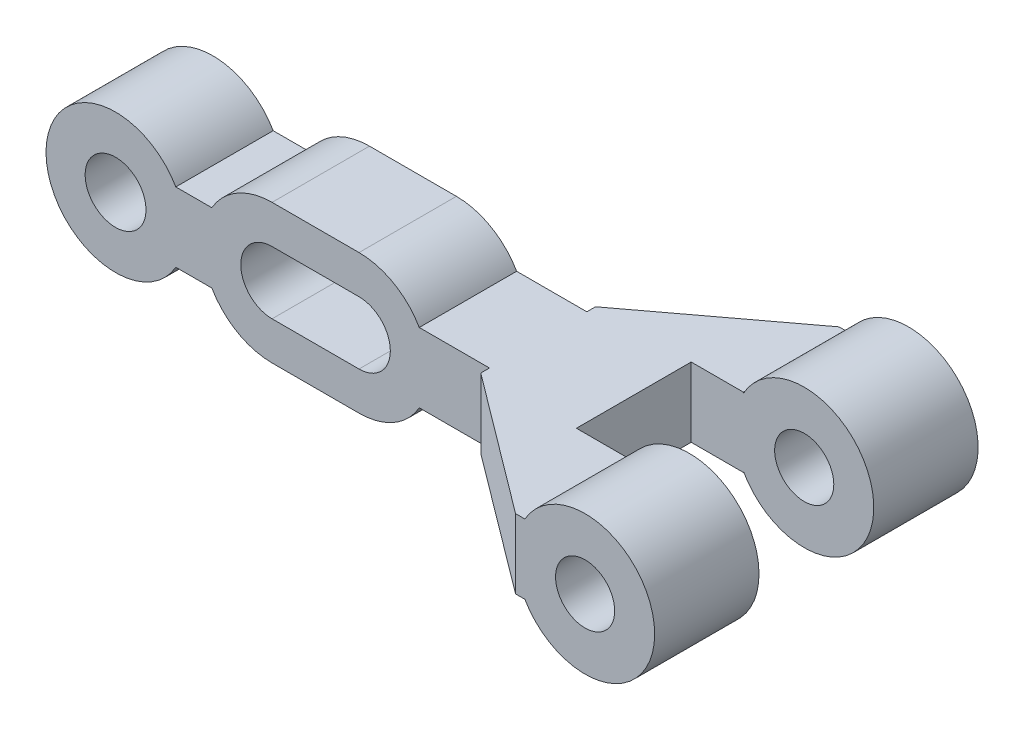
SolidWorks part; units mm, degrees
ref_plane "Спереди" through (0, 0, 0) normal (0, 0, 1) x (1, 0, 0)
ref_plane "Сверху" through (0, 0, 0) normal (0, 1, 0) x (1, 0, 0)
ref_plane "Справа" through (0, 0, 0) normal (1, 0, 0) x (0, 0, -1)
other "Configuration Table"
sketch "Эскиз1" plane through (0, 0, 0) normal (0, 0, 1) x (1, 0, 0)
  circle A0 centre (0, 0) radius 1.7
  circle A1 centre (0, 0) radius 4
  dimension "D1" = 3.4
  dimension "D2" = 8
extrude "Бобышка-Вытянуть1" add sketch "Эскиз1" along normal blind 6
sketch "Эскиз2" plane through (0, 0, 0) normal (0, 1, 0) x (1, 0, 0)
  line L0 (-4, 0) -> (-12, -6)
  line L1 (-12, -6) -> (-12, -12.6)
  line L2 (-12, -12.6) -> (-4, -18.6)
  line L4 (-4, -12.6) -> (-6.5, -12.6)
  line L5 (-6.5, -12.6) -> (-6.5, -6)
  line L6 (-6.5, -6) -> (-4, -6)
  line L7 (-4, 0) -> (-4, -6) construction
  line L9 (3.0677, -9.3) -> (-16.8387, -9.3) construction
  line L10 (-4, -6) -> (4, -6) construction
  line L11 (-4, 0) -> (-3.5, 0)
  line L12 (-3.5, 0) -> (-3.5, -6)
  line L13 (-3.5, -6) -> (-4, -6)
  line L14 (-4, -12.6) -> (-3, -12.6)
  line L15 (-3, -12.6) -> (-3, -18.6)
  line L16 (-3, -18.6) -> (-4, -18.6)
  dimension "D1" = 3.3
  dimension "D2" = 6
  dimension "D3" = 2.5
  dimension "D4" = 5.5
  dimension "D5" = 0.5
  dimension "D6" = 1
extrude "Бобышка-Вытянуть2" add sketch "Эскиз2" along normal blind 2 and the other way blind 2
ref_plane "Плоскость1" through (0, 0, 9.3) normal (0, 0, -1) x (-1, 0, 0)
mirror "Зеркальное отражение1" about plane through (0, 0, 9.3) normal (0, 0, -1) of "Бобышка-Вытянуть1"
sketch "Эскиз3" plane through (0, 0, 9.3) normal (0, 0, -1) x (-1, 0, 0)
  line L0 (19.5, 4) -> (24.5, 4)
  line L1 (12, 2) -> (16.0359, 2)
  line L2 (12, 2) -> (12, -2)
  line L3 (12, -2) -> (16.0359, -2)
  line L5 (19.5, -4) -> (24.5, -4)
  line L6 (19.5, 1.8) -> (24.5, 1.8)
  line L7 (19.5, -1.8) -> (24.5, -1.8)
  line L8 (27.9641, 2) -> (30.0359, 2)
  line L9 (27.9641, -2) -> (30.0359, -2)
  line L10 (-9.7594, 0) -> (59.5703, 0) construction
  line L12 (12, -2) -> (12, 2) construction
  arc A0 (24.5, -1.8) -> (24.5, 1.8) centre (24.5, 0) ccw
  arc A1 (19.5, 1.8) -> (19.5, -1.8) centre (19.5, 0) ccw
  arc A3 (19.5, 4) -> (16.0359, 2) centre (19.5, 0) ccw
  arc A4 (24.5, -4) -> (27.9641, -2) centre (24.5, 0) ccw
  arc A5 (16.0359, -2) -> (19.5, -4) centre (19.5, 0) ccw
  arc A6 (27.9641, 2) -> (24.5, 4) centre (24.5, 0) ccw
  circle A7 centre (33.5, 0) radius 1.75
  arc A8 (30.0359, -2) -> (30.0359, 2) centre (33.5, 0) ccw
  dimension "D6" = 3.5
  dimension "D7" = 8
  dimension "D8" = 8
  dimension "D1" = 21.5
  dimension "D4" = 5
  dimension "D5" = 12.5
  dimension "D9" = 4
  dimension "D11" = 3.6
extrude "Бобышка-Вытянуть3" add sketch "Эскиз3" along normal blind 2.8 and the other way blind 2.8
sketch "Эскиз4" plane through (0, 0, 18.6) normal (0, 0, 1) x (1, 0, 0)
  circle A0 centre (0, 0) radius 2.8
  dimension "D1" = 5.6
sketch "Эскиз5" plane through (0, 0, 6.5) normal (0, 0, -1) x (-1, 0, 0)
  circle A0 centre (33.5, 0) radius 2.8
  dimension "D1" = 5.6
